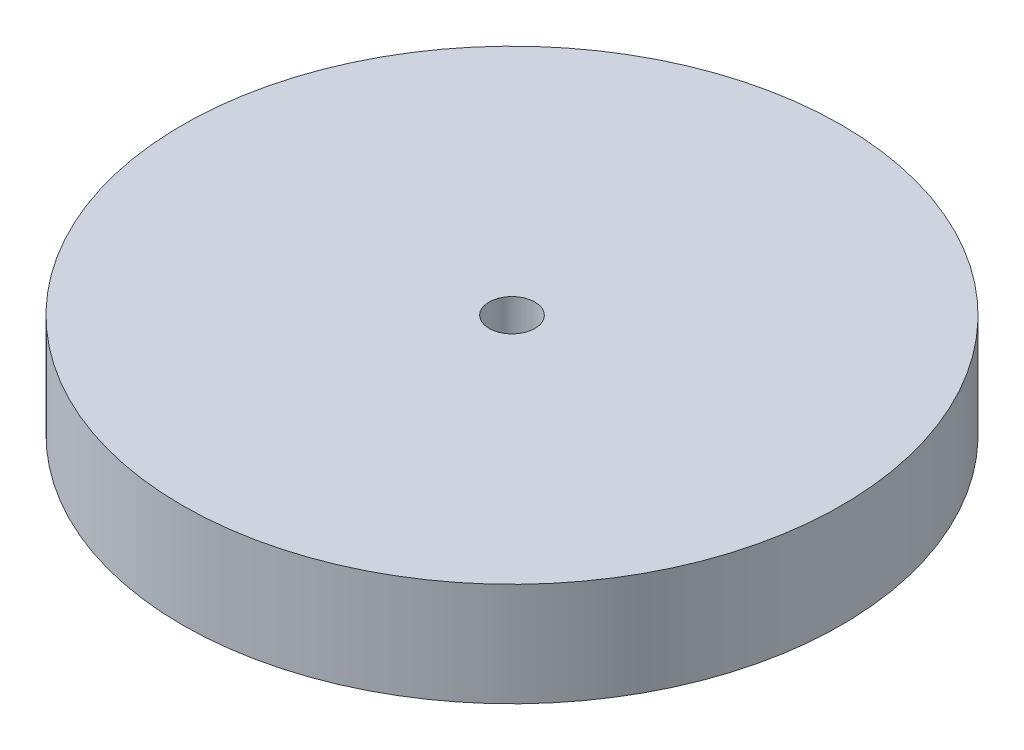
SolidWorks part; units mm, degrees
ref_plane "Front Plane" through (0, 0, 0) normal (0, 0, 1) x (1, 0, 0)
ref_plane "Top Plane" through (0, 0, 0) normal (0, 1, 0) x (1, 0, 0)
ref_plane "Right Plane" through (0, 0, 0) normal (1, 0, 0) x (0, 0, -1)
sketch "Sketch1" plane through (0, 0, 0) normal (0, 1, 0) x (1, 0, 0)
  circle A0 centre (0, 0) radius 60.5
  dimension "D1" = 121
extrude "Boss-Extrude1" add sketch "Sketch1" along normal blind 19
sketch "Sketch2" plane through (0, 19, 0) normal (0, 1, 0) x (1, 0, 0)
  circle A0 centre (0, 0) radius 4.2
  dimension "D1" = 8.4
extrude "Cut-Extrude2" cut sketch "Sketch2" against normal through all
